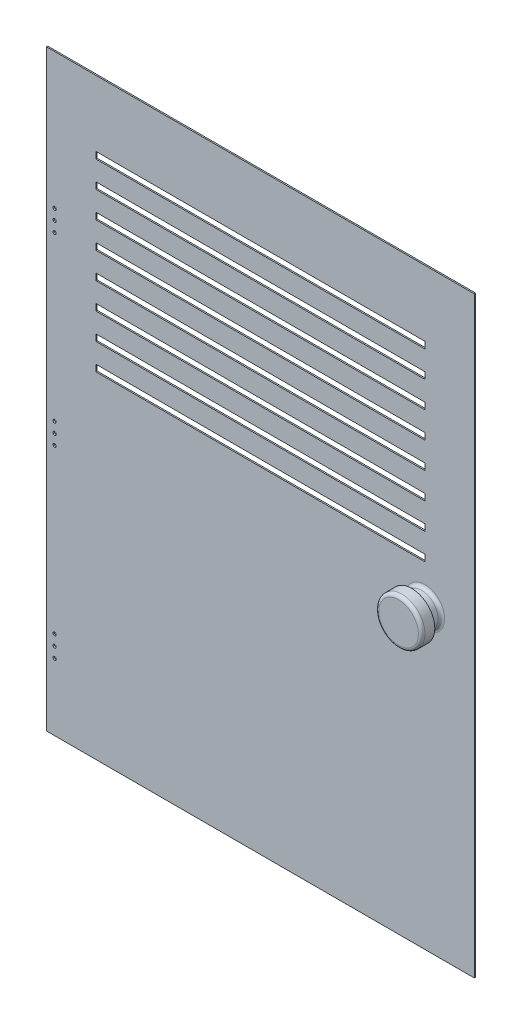
SolidWorks part; units mm, degrees
material "AISI 1020"
ref_plane "Plan de face" through (0, 0, 0) normal (0, 0, 1) x (1, 0, 0)
ref_plane "Plan de dessus" through (0, 0, 0) normal (0, 1, 0) x (1, 0, 0)
ref_plane "Plan de droite" through (0, 0, 0) normal (1, 0, 0) x (0, 0, -1)
sketch "Esquisse1" plane through (0, 0, 0) normal (0, 0, 1) x (1, 0, 0)
  line L1 (-325, 450) -> (325, 450)
  line L2 (-325, 450) -> (-325, -450)
  line L3 (-325, -450) -> (325, -450)
  line L4 (325, 450) -> (325, -450)
  line L5 (-325, 450) -> (325, -450) construction
  line L6 (-325, -450) -> (325, 450) construction
  point P0 (0, 0)
  dimension "D1" = 650
  dimension "D2" = 900
base flange "Tôle de base pliée1" sketch "Esquisse1" thickness 2 reverse thickness direction no parameters "D1"=1
sketch "Esquisse6" plane through (0, 0, 0) normal (0, 0, 1) x (1, 0, 0)
  line L0 (325, 450) -> (-325, 450) construction
  line L1 (-250, 350) -> (250, 350)
  line L2 (-250, 350) -> (-250, 340)
  line L3 (-250, 340) -> (250, 340)
  line L4 (250, 350) -> (250, 340)
  line L5 (-250, 350) -> (250, 340) construction
  line L6 (-250, 340) -> (250, 350) construction
  line L7 (-250, 310) -> (-250, 300)
  line L8 (-250, 310) -> (250, 310)
  line L9 (250, 310) -> (250, 300)
  line L10 (-250, 300) -> (250, 300)
  line L11 (-250, 270) -> (-250, 260)
  line L12 (-250, 270) -> (250, 270)
  line L13 (250, 270) -> (250, 260)
  line L14 (-250, 260) -> (250, 260)
  line L15 (-250, 230) -> (-250, 220)
  line L16 (-250, 230) -> (250, 230)
  line L17 (250, 230) -> (250, 220)
  line L18 (-250, 220) -> (250, 220)
  line L19 (-250, 190) -> (-250, 180)
  line L20 (-250, 190) -> (250, 190)
  line L21 (250, 190) -> (250, 180)
  line L22 (-250, 180) -> (250, 180)
  line L23 (-250, 150) -> (-250, 140)
  line L24 (-250, 150) -> (250, 150)
  line L25 (250, 150) -> (250, 140)
  line L26 (-250, 140) -> (250, 140)
  line L27 (-250, 110) -> (-250, 100)
  line L28 (-250, 110) -> (250, 110)
  line L29 (250, 110) -> (250, 100)
  line L30 (-250, 100) -> (250, 100)
  line L31 (-250, 70) -> (-250, 60)
  line L32 (-250, 70) -> (250, 70)
  line L33 (250, 70) -> (250, 60)
  line L34 (-250, 60) -> (250, 60)
  point P4 (0, 345)
  dimension "D1" = 500
  dimension "D2" = 10
  dimension "D3" = 100
  dimension "D4" = 8
extrude "Enlèv. mat.-Extru.1" cut sketch "Esquisse6" against normal blind 10 normal cut yes
sketch "Esquisse7" plane through (0, 0, 0) normal (0, 0, 1) x (1, 0, 0)
  circle A0 centre (250, 0) radius 25
  point P2 (0, 0)
  dimension "D1" = 50
  dimension "D2" = 250
extrude "Boss.-Extru.1" add sketch "Esquisse7" along normal blind 20
sketch "Esquisse8" plane through (0, 0, 20) normal (0, 0, 1) x (1, 0, 0)
  circle A0 centre (250, 0) radius 35
  circle A1 centre (250, 0) radius 25 construction
  dimension "D1" = 10
extrude "Boss.-Extru.2" add sketch "Esquisse8" along normal blind 20
fillet "Congé1" radius 5 3 edges at (285, 0, 40) (275, 0, 20) (275, 0, 0)
sketch "Esquisse9" plane through (0, 0, 0) normal (0, 0, 1) x (1, 0, 0)
  circle A0 centre (-312.5, 243.7753) radius 2.5
  circle A1 centre (-312.5, 227.7753) radius 2.5
  circle A2 centre (-312.5, 211.7753) radius 2.5
  circle A3 centre (-312.5, -36.2247) radius 2.5
  circle A4 centre (-312.5, -52.2247) radius 2.5
  circle A5 centre (-312.5, -68.2247) radius 2.5
  circle A6 centre (-312.5, -316.2247) radius 2.5
  circle A7 centre (-312.5, -332.2247) radius 2.5
  circle A8 centre (-312.5, -348.2247) radius 2.5
  dimension "D1" = 5
  dimension "D3" = 248
  dimension "D2" = 3
extrude "Enlèv. mat.-Extru.2" cut sketch "Esquisse9" against normal blind 20 normal cut yes
sketch "Lignes de pliage1" [suppressed] plane through (0, 0, 0) normal (0, 1, 0) x (1, 0, 0)
sketch "Cube de visualisation1" [suppressed] plane through (0, 0, 0) normal (0, 1, 0) x (1, 0, 0)
sheet metal parameters "Tôlerie1" thickness 2 parameters "D1"=1
flat pattern "Etat déplié1" [suppressed]
sketch "Lignes de pliage2" plane through (0, 0, 0) normal (0, 1, 0) x (1, 0, 0)
sketch3d "Cube de visualisation2" [suppressed]
  line L0 (-325, 450, 0) -> (-325, -450, 0) construction
  line L1 (325, 450, 0) -> (325, -450, 0) construction
  line L2 (-325, 450, 0) -> (325, 450, 0) construction
  line L3 (-325, -450, 0) -> (325, -450, 0) construction
sheet metal parameters "Tôlerie2" thickness 2 parameters "D1"=1
flat pattern "Etat déplié1"
sketch "Lignes de pliage2" plane through (0, 0, 0) normal (0, 1, 0) x (1, 0, 0)
sketch3d "Cube de visualisation2" [suppressed]
  line L0 (325, 450, 0) -> (325, -450, 0) construction
  line L1 (-325, 450, 0) -> (-325, -450, 0) construction
  line L2 (325, 450, 0) -> (-325, 450, 0) construction
  line L3 (325, -450, 0) -> (-325, -450, 0) construction
sheet metal parameters "Tôlerie3" thickness 2 parameters "D1"=1
flat pattern "Etat déplié1"
sketch "Lignes de pliage2" plane through (0, 0, 0) normal (0, 1, 0) x (1, 0, 0)
sketch3d "Cube de visualisation2" [suppressed]
  line L0 (325, 450, 0) -> (325, -450, 0) construction
  line L1 (-325, 450, 0) -> (-325, -450, 0) construction
  line L2 (325, 450, 0) -> (-325, 450, 0) construction
  line L3 (325, -450, 0) -> (-325, -450, 0) construction
sheet metal parameters "Tôlerie4" thickness 2 parameters "D1"=1
flat pattern "Etat déplié1"
sketch "Lignes de pliage2" plane through (0, 0, 0) normal (0, 1, 0) x (1, 0, 0)
sketch3d "Cube de visualisation2" [suppressed]
  line L0 (325, 450, 0) -> (325, -450, 0) construction
  line L1 (-325, 450, 0) -> (-325, -450, 0) construction
  line L2 (325, 450, 0) -> (-325, 450, 0) construction
  line L3 (325, -450, 0) -> (-325, -450, 0) construction
sheet metal parameters "Tôlerie5" thickness 2 parameters "D1"=1
flat pattern "Etat déplié1"
sketch "Lignes de pliage2" plane through (0, 0, 0) normal (0, 1, 0) x (1, 0, 0)
sketch3d "Cube de visualisation2" [suppressed]
  line L0 (325, 450, 0) -> (325, -450, 0) construction
  line L1 (-325, 450, 0) -> (-325, -450, 0) construction
  line L2 (325, 450, 0) -> (-325, 450, 0) construction
  line L3 (325, -450, 0) -> (-325, -450, 0) construction
